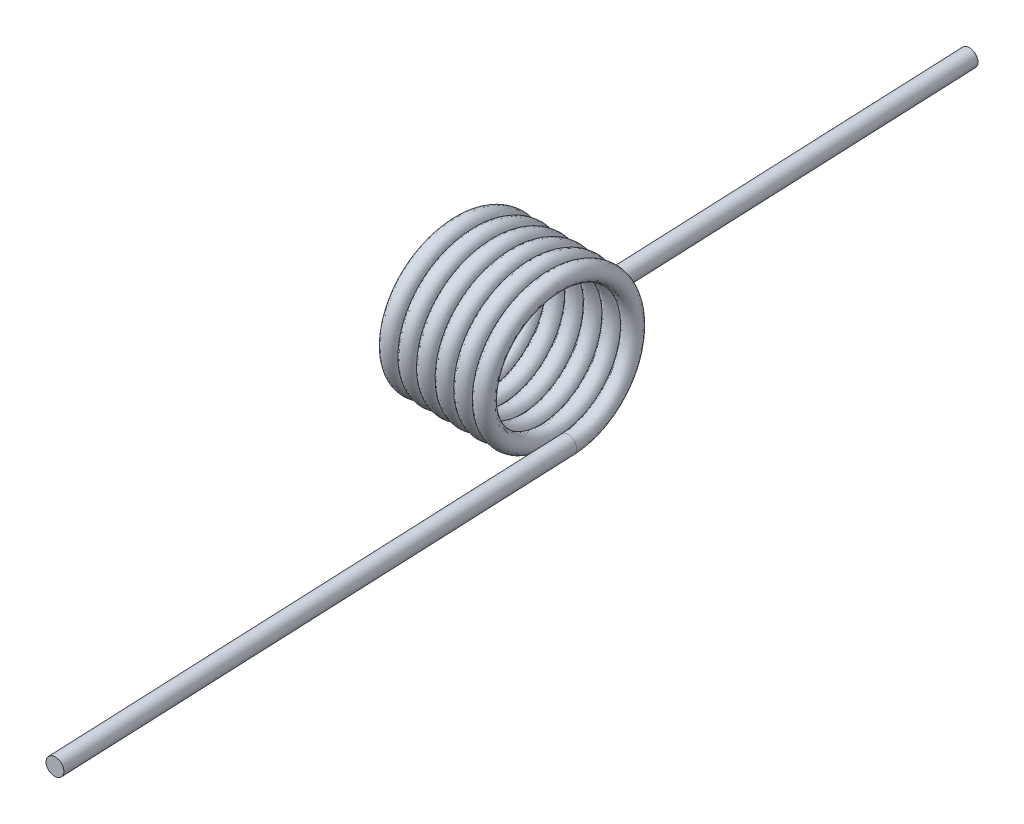
SolidWorks part; units mm, degrees
ref_plane "Front" through (0, 0, 0) normal (0, 0, 1) x (1, 0, 0)
ref_plane "Top" through (0, 0, 0) normal (0, 1, 0) x (1, 0, 0)
ref_plane "Right" through (0, 0, 0) normal (1, 0, 0) x (0, 0, -1)
sketch "Sketch1" plane through (0, 0, 0) normal (1, 0, 0) x (0, 0, -1)
  line L0 (0, -1.0795) -> (0, -1.3843) construction
  line L1 (0, -1.3843) -> (9.525, -1.3843) construction
  line L2 (0, -1.3843) -> (-9.525, -1.3843) construction
  line L3 (0, 0) -> (1.3843, 0) construction
  line L4 (0, 0) -> (0, -1.3843) construction
  line L5 (-9.525, -1.3843) -> (-9.525, -1.0795) construction
  line L6 (-9.525, -1.0795) -> (0, -1.0795) construction
  line L7 (9.525, -1.3843) -> (9.525, -1.0795) construction
  line L8 (9.525, -1.0795) -> (0, -1.0795) construction
  circle A0 centre (0, 0) radius 1.3843 construction
  circle A1 centre (0, 0) radius 0.8509 construction
  circle A2 centre (0, 0) radius 1.2319 construction
  point P7 (0, -1.2319)
  point P10 (0, 1.3843)
  dimension "OD" = 2.7686
  dimension "For Shaft Diameter" = 1.7018
  dimension "Wire Diameter" = 0.3048
  dimension "Leg Length" = 9.525
  dimension "Deflection Angle" = 180
sketch "Sketch2" plane through (0, 0, 0) normal (1, 0, 0) x (0, 0, -1)
  circle A0 centre (0, 0) radius 1.2319 construction
  circle A2 centre (0, 0) radius 1.2319
curve "Helix/Spiral1" pitch 0.3302 height 1.9812 turns 6
ref_plane "Plane1" through (0, -1.2319, 0) normal (-0.0426, 0, -0.9991) x (0.9988, -0.0232, -0.0426)
sketch "Sketch3" plane through (0, -1.2319, 0) normal (-0.0426, 0, -0.9991) x (0.9988, -0.0232, -0.0426)
  circle A0 centre (0, 0) radius 0.1524
  dimension "D1" = 0.3048
sweep "Sweep1" add profiles "Sketch3" path "Helix/Spiral1"
sketch "Sketch4" plane through (0, 0, 0) normal (0.0426, 0, 0.9991) x (-0.9988, 0.0232, 0.0426)
  circle A1 centre (-0.0286, 1.2316) radius 0.1524
  circle A2 centre (-0.0286, 1.2316) radius 0.1524
  dimension "D1" = 0
extrude "Extrude1" add sketch "Sketch4" along normal blind 9.525
sketch "Sketch5" plane through (-0.0036, 0, -0.0844) normal (-0.0426, 0, -0.9991) x (0.9978, 0.0506, -0.0426)
  circle A1 centre (-2.0391, 1.1303) radius 0.1524
  circle A2 centre (-2.0391, 1.1303) radius 0.1524
  dimension "D1" = 0
extrude "Extrude2" add sketch "Sketch5" along normal blind 9.525
sketch "Sketch6" plane through (0, 0, 0) normal (1, 0, 0) x (0, 0, -1)
  circle A2 centre (0, 0) radius 1.0795 construction
equation "\"D4@Helix/Spiral1\" = \"Wire Diameter@Sketch1\" + .001"
equation "\"D1@Sketch3\"=\"Wire Diameter@Sketch1\""
equation "\"D1@Extrude2\"=\"Leg Length@Sketch1\""
equation "\"Leg Length@Extrude1\"=\"Leg Length@Sketch1\""
